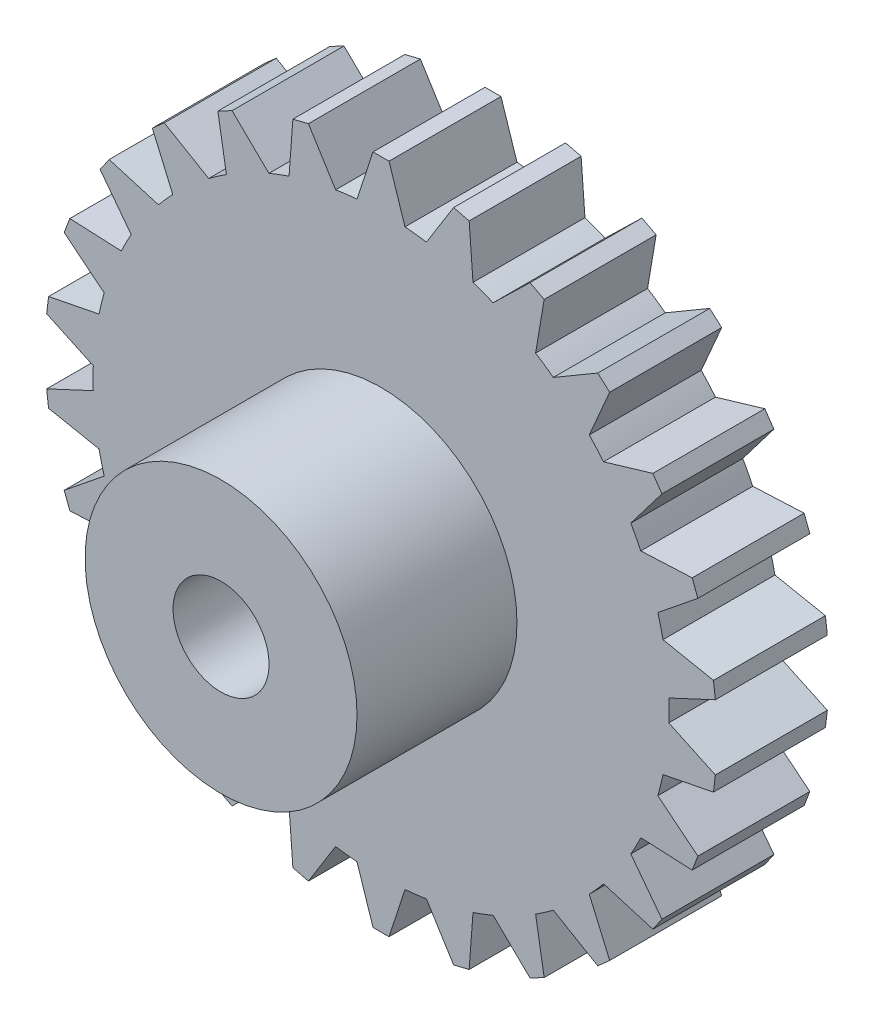
SolidWorks part; units mm, degrees
ref_plane "Front Plane" through (0, 0, 0) normal (0, 0, 1) x (1, 0, 0)
ref_plane "Top Plane" through (0, 0, 0) normal (0, 1, 0) x (1, 0, 0)
ref_plane "Right Plane" through (0, 0, 0) normal (1, 0, 0) x (0, 0, -1)
sketch "Sketch1" plane through (0, 0, 0) normal (0, 0, 1) x (1, 0, 0)
  line L0 (0, 0) -> (0, 21.7596) construction
  line L17 (4.5387, 20.5037) -> (2.8363, 17.7751)
  line L18 (4.5387, 20.5037) -> (5.5097, 20.2643)
  line L19 (5.5097, 20.2643) -> (5.7491, 17.0572)
  line L20 (9.3137, 18.8217) -> (7.0077, 16.5799)
  line L21 (9.3137, 18.8217) -> (10.1991, 18.3569)
  line L22 (10.1991, 18.3569) -> (9.6641, 15.1857)
  line L23 (13.5474, 16.0458) -> (10.7719, 14.421)
  line L24 (13.5474, 16.0458) -> (14.2959, 15.3827)
  line L25 (14.2959, 15.3827) -> (13.0175, 12.4316)
  line L26 (16.9937, 12.3375) -> (13.9101, 11.4241)
  line L27 (-1.5, 17.9374) -> (1.5, 17.9374) construction
  line L28 (-0.5, 20.994) -> (0.5, 20.994)
  line L29 (-0.5, 20.994) -> (-1.5, 17.9374)
  line L30 (0.5, 20.994) -> (1.5, 17.9374)
  line L31 (16.9937, 12.3375) -> (17.5618, 11.5145)
  line L32 (17.5618, 11.5145) -> (15.6143, 8.9551)
  line L33 (19.4525, 7.9121) -> (16.2398, 7.7632)
  line L34 (19.4525, 7.9121) -> (19.8071, 6.9771)
  line L35 (19.8071, 6.9771) -> (17.3037, 4.9582)
  line L36 (20.7807, 3.0269) -> (17.6258, 3.6512)
  line L37 (20.7807, 3.0269) -> (20.9012, 2.0342)
  line L38 (20.9012, 2.0342) -> (17.9874, 0.6731)
  line L39 (20.9012, -2.0342) -> (17.9874, -0.6731)
  line L40 (20.9012, -2.0342) -> (20.7807, -3.0269)
  line L41 (20.7807, -3.0269) -> (17.6258, -3.6512)
  line L42 (19.8071, -6.9771) -> (17.3037, -4.9582)
  line L43 (19.8071, -6.9771) -> (19.4525, -7.9121)
  line L44 (19.4525, -7.9121) -> (16.2398, -7.7632)
  line L45 (17.5618, -11.5145) -> (15.6143, -8.9551)
  line L46 (17.5618, -11.5145) -> (16.9937, -12.3375)
  line L47 (16.9937, -12.3375) -> (13.9101, -11.4241)
  line L48 (14.2959, -15.3827) -> (13.0175, -12.4316)
  line L49 (14.2959, -15.3827) -> (13.5474, -16.0458)
  line L50 (13.5474, -16.0458) -> (10.7719, -14.421)
  line L51 (10.1991, -18.3569) -> (9.6641, -15.1857)
  line L52 (10.1991, -18.3569) -> (9.3137, -18.8217)
  line L53 (9.3137, -18.8217) -> (7.0077, -16.5799)
  line L54 (5.5097, -20.2643) -> (5.7491, -17.0572)
  line L55 (5.5097, -20.2643) -> (4.5387, -20.5037)
  line L56 (4.5387, -20.5037) -> (2.8363, -17.7751)
  line L57 (0.5, -20.994) -> (1.5, -17.9374)
  line L58 (0.5, -20.994) -> (-0.5, -20.994)
  line L59 (-0.5, -20.994) -> (-1.5, -17.9374)
  line L60 (-4.5387, -20.5037) -> (-2.8363, -17.7751)
  line L61 (-4.5387, -20.5037) -> (-5.5097, -20.2643)
  line L62 (-5.5097, -20.2643) -> (-5.7491, -17.0572)
  line L63 (-9.3137, -18.8217) -> (-7.0077, -16.5799)
  line L64 (-9.3137, -18.8217) -> (-10.1991, -18.3569)
  line L65 (-10.1991, -18.3569) -> (-9.6641, -15.1857)
  line L66 (-13.5474, -16.0458) -> (-10.7719, -14.421)
  line L67 (-13.5474, -16.0458) -> (-14.2959, -15.3827)
  line L68 (-14.2959, -15.3827) -> (-13.0175, -12.4316)
  line L69 (-16.9937, -12.3375) -> (-13.9101, -11.4241)
  line L70 (-16.9937, -12.3375) -> (-17.5618, -11.5145)
  line L71 (-17.5618, -11.5145) -> (-15.6143, -8.9551)
  line L72 (-19.4525, -7.9121) -> (-16.2398, -7.7632)
  line L73 (-19.4525, -7.9121) -> (-19.8071, -6.9771)
  line L74 (-19.8071, -6.9771) -> (-17.3037, -4.9582)
  line L75 (-20.7807, -3.0269) -> (-17.6258, -3.6512)
  line L76 (-20.7807, -3.0269) -> (-20.9012, -2.0342)
  line L77 (-20.9012, -2.0342) -> (-17.9874, -0.6731)
  line L78 (-20.9012, 2.0342) -> (-17.9874, 0.6731)
  line L79 (-20.9012, 2.0342) -> (-20.7807, 3.0269)
  line L80 (-20.7807, 3.0269) -> (-17.6258, 3.6512)
  line L81 (-19.8071, 6.9771) -> (-17.3037, 4.9582)
  line L82 (-19.8071, 6.9771) -> (-19.4525, 7.9121)
  line L83 (-19.4525, 7.9121) -> (-16.2398, 7.7632)
  line L84 (-17.5618, 11.5145) -> (-15.6143, 8.9551)
  line L85 (-17.5618, 11.5145) -> (-16.9937, 12.3375)
  line L86 (-16.9937, 12.3375) -> (-13.9101, 11.4241)
  line L87 (-14.2959, 15.3827) -> (-13.0175, 12.4316)
  line L88 (-14.2959, 15.3827) -> (-13.5474, 16.0458)
  line L89 (-13.5474, 16.0458) -> (-10.7719, 14.421)
  line L90 (-10.1991, 18.3569) -> (-9.6641, 15.1857)
  line L91 (-10.1991, 18.3569) -> (-9.3137, 18.8217)
  line L92 (-9.3137, 18.8217) -> (-7.0077, 16.5799)
  line L93 (-5.5097, 20.2643) -> (-5.7491, 17.0572)
  line L94 (-5.5097, 20.2643) -> (-4.5387, 20.5037)
  line L95 (-4.5387, 20.5037) -> (-2.8363, 17.7751)
  circle A0 centre (0, 0) radius 8.5
  arc A17 (-1.5, 17.9374) -> (-2.8363, 17.7751) centre (0, 0) ccw
  arc A18 (-13.5474, 16.0458) -> (-14.2959, 15.3827) centre (0, 0) ccw construction
  arc A19 (2.8363, 17.7751) -> (1.5, 17.9374) centre (0, 0) ccw
  arc A20 (7.0077, 16.5799) -> (5.7491, 17.0572) centre (0, 0) ccw
  arc A21 (10.7719, 14.421) -> (9.6641, 15.1857) centre (0, 0) ccw
  arc A22 (13.9101, 11.4241) -> (13.0175, 12.4316) centre (0, 0) ccw
  arc A23 (16.2398, 7.7632) -> (15.6143, 8.9551) centre (0, 0) ccw
  arc A24 (17.6258, 3.6512) -> (17.3037, 4.9582) centre (0, 0) ccw
  arc A25 (17.9874, -0.6731) -> (17.9874, 0.6731) centre (0, 0) ccw
  arc A26 (17.3037, -4.9582) -> (17.6258, -3.6512) centre (0, 0) ccw
  arc A27 (15.6143, -8.9551) -> (16.2398, -7.7632) centre (0, 0) ccw
  arc A28 (13.0175, -12.4316) -> (13.9101, -11.4241) centre (0, 0) ccw
  arc A29 (9.6641, -15.1857) -> (10.7719, -14.421) centre (0, 0) ccw
  arc A30 (5.7491, -17.0572) -> (7.0077, -16.5799) centre (0, 0) ccw
  arc A31 (1.5, -17.9374) -> (2.8363, -17.7751) centre (0, 0) ccw
  arc A32 (-2.8363, -17.7751) -> (-1.5, -17.9374) centre (0, 0) ccw
  arc A33 (-7.0077, -16.5799) -> (-5.7491, -17.0572) centre (0, 0) ccw
  arc A34 (-10.7719, -14.421) -> (-9.6641, -15.1857) centre (0, 0) ccw
  arc A35 (-13.9101, -11.4241) -> (-13.0175, -12.4316) centre (0, 0) ccw
  arc A36 (-16.2398, -7.7632) -> (-15.6143, -8.9551) centre (0, 0) ccw
  arc A37 (-17.6258, -3.6512) -> (-17.3037, -4.9582) centre (0, 0) ccw
  arc A38 (-17.9874, 0.6731) -> (-17.9874, -0.6731) centre (0, 0) ccw
  arc A39 (-17.3037, 4.9582) -> (-17.6258, 3.6512) centre (0, 0) ccw
  arc A40 (-15.6143, 8.9551) -> (-16.2398, 7.7632) centre (0, 0) ccw
  arc A41 (-13.0175, 12.4316) -> (-13.9101, 11.4241) centre (0, 0) ccw
  arc A42 (-9.6641, 15.1857) -> (-10.7719, 14.421) centre (0, 0) ccw
  arc A43 (-5.7491, 17.0572) -> (-7.0077, 16.5799) centre (0, 0) ccw
  arc A44 (-9.3137, 18.8217) -> (-10.1991, 18.3569) centre (0, 0) ccw construction
  arc A45 (-4.5387, 20.5037) -> (-5.5097, 20.2643) centre (0, 0) ccw construction
  arc A46 (5.5097, 20.2643) -> (-0.5, 20.994) centre (0, 0) ccw construction
  arc A47 (10.1991, 18.3569) -> (9.3137, 18.8217) centre (0, 0) ccw construction
  arc A48 (14.2959, 15.3827) -> (13.5474, 16.0458) centre (0, 0) ccw construction
  arc A49 (17.5618, 11.5145) -> (16.9937, 12.3375) centre (0, 0) ccw construction
  arc A50 (19.8071, 6.9771) -> (19.4525, 7.9121) centre (0, 0) ccw construction
  arc A51 (19.4525, -7.9121) -> (19.8071, -6.9771) centre (0, 0) ccw construction
  arc A52 (16.9937, -12.3375) -> (17.5618, -11.5145) centre (0, 0) ccw construction
  arc A53 (9.3137, -18.8217) -> (10.1991, -18.3569) centre (0, 0) ccw construction
  arc A54 (13.5474, -16.0458) -> (14.2959, -15.3827) centre (0, 0) ccw construction
  arc A55 (-0.5, -20.994) -> (0.5, -20.994) centre (0, 0) ccw construction
  arc A56 (4.5387, -20.5037) -> (5.5097, -20.2643) centre (0, 0) ccw construction
  arc A57 (-5.5097, -20.2643) -> (-4.5387, -20.5037) centre (0, 0) ccw construction
  arc A58 (-10.1991, -18.3569) -> (-9.3137, -18.8217) centre (0, 0) ccw construction
  arc A59 (-14.2959, -15.3827) -> (-13.5474, -16.0458) centre (0, 0) ccw construction
  arc A60 (-19.8071, -6.9771) -> (-19.4525, -7.9121) centre (0, 0) ccw construction
  arc A61 (-20.9012, -2.0342) -> (-20.7807, -3.0269) centre (0, 0) ccw construction
  arc A62 (-20.7807, 3.0269) -> (-20.9012, 2.0342) centre (0, 0) ccw construction
  arc A63 (-19.4525, 7.9121) -> (-19.8071, 6.9771) centre (0, 0) ccw construction
  arc A64 (-16.9937, 12.3375) -> (-17.5618, 11.5145) centre (0, 0) ccw construction
  arc A65 (-17.5618, -11.5145) -> (-16.9937, -12.3375) centre (0, 0) ccw construction
  arc A66 (20.9012, 2.0342) -> (20.7807, 3.0269) centre (0, 0) ccw construction
  arc A67 (20.7807, -3.0269) -> (20.9012, -2.0342) centre (0, 0) ccw construction
  point P41 (0, 0)
  point P112 (0, 0)
  dimension "D1" = 17
  dimension "D2" = 42
  dimension "D3" = 3
  dimension "D6" = 36
  dimension "D4" = 1.5
  dimension "D5" = 1.5
  dimension "D7" = 1
  dimension "D8" = 26
extrude "Boss-Extrude1" add sketch "Sketch1" along normal blind 7 contours A17 | L93 A43 L92 L91 L90 A42 L89 L88 L87 A41 L86 L85 L84 A40 L83 L82 L81 A39 L80 L79 L78 A38 L77 L76 L75 A37 L74 L73 L72 A36 L71 L70 L69 A35 L68 L67 L66 A34 L65 L64 L63 A33 L62 L61 L60 A32 L59 L58 L57 A31 L56 region at (4.8824, 19.8087, 0)
sketch "Sketch2" plane through (0, 0, 7) normal (0, 0, 1) x (1, 0, 0)
  circle A0 centre (0, 0) radius 8.5
  circle A1 centre (0, 0) radius 3
  dimension "D1" = 6
extrude "Boss-Extrude2" add sketch "Sketch2" along normal blind 10 and the other way up to surface (7 mm away) other way up to face at (8.5, 0, 0)
